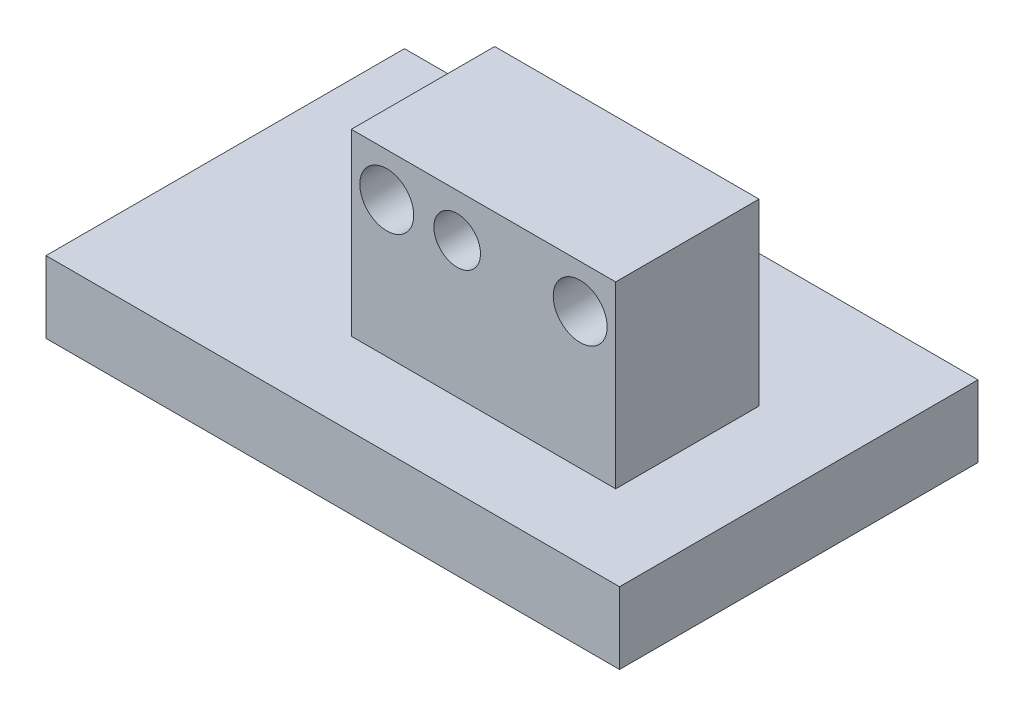
SolidWorks part; units mm, degrees
ref_plane "Front Plane" through (0, 0, 0) normal (0, 0, 1) x (1, 0, 0)
ref_plane "Top Plane" through (0, 0, 0) normal (0, 1, 0) x (1, 0, 0)
ref_plane "Right Plane" through (0, 0, 0) normal (1, 0, 0) x (0, 0, -1)
sketch "Sketch1" plane through (0, 0, 0) normal (0, 1, 0) x (1, 0, 0)
  line L0 (-8.9655, -3.4477) -> (27.9061, -3.4477) construction
  line L1 (-40, -25) -> (40, -25)
  line L2 (-40, -25) -> (-40, 25)
  line L3 (-40, 25) -> (40, 25)
  line L4 (40, -25) -> (40, 25)
  line L5 (-40, -25) -> (40, 25) construction
  line L6 (-40, 25) -> (40, -25) construction
  line L7 (-8.9655, -13.4477) -> (27.9061, -13.4477)
  line L8 (-8.9655, -13.4477) -> (-8.9655, 6.5523)
  line L9 (-8.9655, 6.5523) -> (27.9061, 6.5523)
  line L10 (27.9061, -13.4477) -> (27.9061, 6.5523)
  line L11 (-5.5297, -13.4477) -> (-5.5297, 6.5523) construction
  line L12 (9.4703, 6.5523) -> (9.4703, -13.4477) construction
  line L13 (21.4703, -13.4477) -> (21.4703, 6.5523) construction
  line L14 (-23.4382, 22.4306) -> (-23.4382, 8.4306) construction
  line L15 (-33.4382, 8.4306) -> (-13.4382, 8.4306)
  line L16 (-33.4382, 8.4306) -> (-33.4382, 22.4306)
  line L17 (-33.4382, 22.4306) -> (-13.4382, 22.4306)
  line L18 (-13.4382, 8.4306) -> (-13.4382, 22.4306)
  line L19 (-33.4382, 15.4306) -> (-13.4382, 15.4306) construction
  circle A0 centre (-30.9382, 20.4306) radius 1.3182
  circle A1 centre (-15.9382, 20.4306) radius 1.3182
  circle A2 centre (-15.9382, 10.4306) radius 1.3182
  circle A3 centre (-30.9382, 10.4306) radius 1.3182
  point P0 (0, 0)
  dimension "D1" = 50
  dimension "D2" = 80
  dimension "D3" = 15
  dimension "D4" = 20
  dimension "D5" = 12
  dimension "D6" = 20
  dimension "D7" = 14
  dimension "D8" = 10
  dimension "D9" = 15
extrude "Main Plate" add sketch "Sketch1" against normal blind 10 contours L1 L4 L3 L2
extrude "Boss-Extrude2" add sketch "Sketch1<3>" along normal blind 25 contours L7 L10 L9 L8 region at (9.4703, 0, 3.4477)
sketch "Sketch1<3>" plane through (0, 0, 0) normal (0, 1, 0) x (1, 0, 0) same geometry as "Sketch1"
sketch "Sketch2" plane through (0, 0, 13.4477) normal (0, 0, 1) x (1, 0, 0)
  line L0 (9.4703, 25) -> (9.4703, 0) construction
  line L1 (-8.9655, 25) -> (27.9061, 25) construction
  line L2 (-8.9655, 0) -> (27.9061, 0) construction
  circle A0 centre (-4.0183, 18.9612) radius 3.761
  circle A1 centre (22.9589, 18.9612) radius 3.761
  circle A2 centre (5.7986, 18.9612) radius 3.25
  dimension "D1" = 6.5
extrude "Cut-Extrude1" cut sketch "Sketch2" against normal up to surface (20 mm away) up to face at (9.4703, 12.5, -6.5523)
